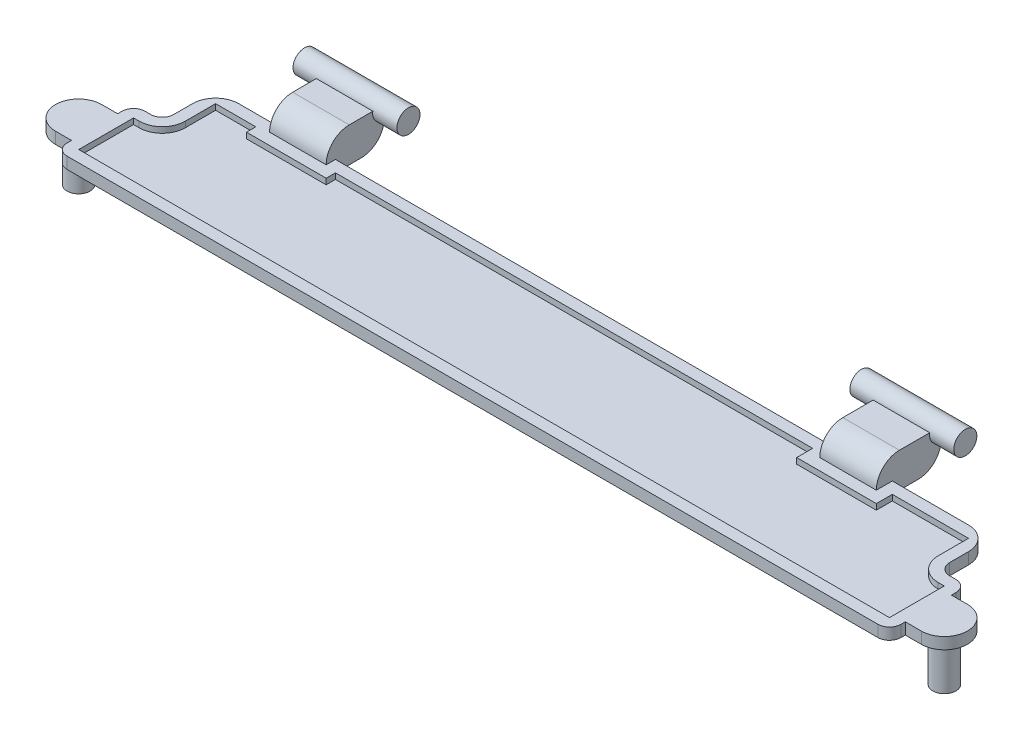
SolidWorks part; units mm, degrees
material "Alloy Steel"
ref_plane "Front Plane" through (0, 0, 0) normal (0, 0, 1) x (1, 0, 0)
ref_plane "Top Plane" through (0, 0, 0) normal (0, 1, 0) x (1, 0, 0)
ref_plane "Right Plane" through (0, 0, 0) normal (1, 0, 0) x (0, 0, -1)
sketch "Sketch1" plane through (0, 0, 0) normal (0, 1, 0) x (1, 0, 0)
  line L0 (0, 0) -> (67.22, 0) construction
  circle A0 centre (67.22, 0) radius 2
  circle A1 centre (0, 0) radius 2
extrude "Boss-Extrude1" add sketch "Sketch1" along normal blind 2.5
sketch "Sketch2" plane through (0, 2.5, 0) normal (0, 1, 0) x (1, 0, 0)
  line L3 (0, 3.3731) -> (0, 8)
  line L4 (0, 8) -> (67.2203, 8)
  line L5 (67.2203, 3.3731) -> (67.2203, 8)
  line L6 (69.7452, -3.3731) -> (-2.4854, -3.3731)
  line L7 (69.7452, -3.3731) -> (69.7452, 3.3731)
  line L8 (69.7452, 3.3731) -> (67.2203, 3.3731)
  line L9 (-2.4854, -3.3731) -> (-2.4854, 3.3731)
  line L12 (0, 3.3731) -> (-2.4854, 3.3731)
  point P4 (32.05, 0)
  point P7 (32.05, 0)
extrude "Boss-Extrude3" add sketch "Sketch2" along normal blind 1
fillet "Fillet1" radius 1 6 edges at (0, 3, -3.3731) (67.2203, 3, -3.3731) (69.7452, 3, -3.3731) (69.7452, 3, 3.3731) (-2.4854, 3, 3.3731) (-2.4854, 3, -3.3731)
sketch "Sketch3" plane through (0, 3.5, 0) normal (0, 1, 0) x (1, 0, 0)
  line L0 (33.6102, 8) -> (4.9902, 8) construction
  line L1 (67.2203, 8) -> (0, 8) construction
  line L2 (33.6102, 8) -> (62.2302, 8) construction
  line L3 (4.9902, 8) -> (4.9902, 12.2253) construction
  line L4 (4.9902, 12.2253) -> (10.8698, 12.2253) construction
  line L5 (62.2302, 8) -> (62.2302, 12.2253) construction
  line L6 (62.2302, 12.2253) -> (50.1098, 12.2253) construction
  line L7 (7.93, 12.2253) -> (7.93, 7.1953) construction
  line L8 (56.17, 12.2253) -> (56.17, 6.616) construction
  line L9 (10.8698, 12.2253) -> (50.1115, 12.2253) construction
  line L10 (5.48, 7.1953) -> (10.38, 7.1953)
  line L11 (5.48, 7.1953) -> (5.48, 12.2253)
  line L12 (5.48, 12.2253) -> (10.38, 12.2253)
  line L13 (10.38, 7.1953) -> (10.38, 12.2253)
  line L14 (5.48, 7.1953) -> (10.38, 12.2253) construction
  line L15 (5.48, 12.2253) -> (10.38, 7.1953) construction
  line L16 (58.62, 6.616) -> (53.72, 6.616)
  line L17 (58.62, 6.616) -> (58.62, 12.2253)
  line L18 (58.62, 12.2253) -> (53.72, 12.2253)
  line L19 (53.72, 6.616) -> (53.72, 12.2253)
  line L20 (58.62, 6.616) -> (53.72, 12.2253) construction
  line L21 (58.62, 12.2253) -> (53.72, 6.616) construction
  point P13 (7.93, 9.7103)
  point P18 (56.17, 9.4207)
  dimension "D1" = 28.62
extrude "Boss-Extrude4" add sketch "Sketch3" along normal blind 2 and the other way blind 1
sketch "Sketch4" plane through (5.48, 0, 0) normal (-1, 0, 0) x (0, 0, 1)
  line L0 (-12.2253, 2.5) -> (-12.2253, 5.5) construction
  circle A0 centre (-12.2253, 5.3165) radius 1
extrude "Boss-Extrude5" add sketch "Sketch4" along normal blind 2 and the other way blind 7
sketch "Sketch5" plane through (53.72, 0, 0) normal (-1, 0, 0) x (0, 0, 1)
  circle A0 centre (-12.2253, 5.3165) radius 1
extrude "Boss-Extrude6" add sketch "Sketch5" along normal blind 2 and the other way blind 7
fillet "Fillet2" radius 2 2 edges at (7.93, 5.5, -7.1953) (56.17, 5.5, -6.616)
fillet "Fillet3" radius 2 1 edges at (56.17, 2.5, -12.2253)
sketch "Sketch6" plane through (0, 3.5, 0) normal (0, 1, 0) x (1, 0, 0)
  line L32 (59.62, 5.616) -> (52.72, 5.616)
  line L33 (59.62, 5.616) -> (52.72, 5.616)
  line L34 (52.72, 7) -> (11.38, 7)
  line L35 (11.38, 7) -> (11.38, 6.1953)
  line L36 (52.72, 5.616) -> (52.72, 7)
  line L37 (4.48, 6.1953) -> (4.48, 7)
  line L38 (4.48, 7) -> (1, 7)
  line L39 (1, 7) -> (1, 4.3731)
  line L40 (-1, 2.3731) -> (-1.4854, 2.3731)
  line L41 (-1.4854, 2.3731) -> (-1.4854, -2.3731)
  line L42 (-1.4854, -2.3731) -> (68.7452, -2.3731)
  line L43 (68.7452, -2.3731) -> (68.7452, 2.3731)
  line L44 (68.7452, 2.3731) -> (68.2203, 2.3731)
  line L45 (66.2203, 4.3731) -> (66.2203, 7)
  line L46 (66.2203, 7) -> (59.62, 7)
  line L47 (52.72, 5.616) -> (52.72, 7)
  line L48 (11.38, 6.1953) -> (4.48, 6.1953)
  line L49 (59.62, 7) -> (59.62, 5.616)
  line L50 (52.72, 7) -> (11.38, 7)
  line L51 (11.38, 7) -> (11.38, 6.1953)
  line L52 (11.38, 6.1953) -> (4.48, 6.1953)
  line L53 (4.48, 6.1953) -> (4.48, 7)
  line L54 (4.48, 7) -> (1, 7)
  line L55 (1, 7) -> (1, 4.3731)
  line L56 (-1, 2.3731) -> (-1.4854, 2.3731)
  line L57 (-1.4854, 2.3731) -> (-1.4854, -2.3731)
  line L58 (-1.4854, -2.3731) -> (68.7452, -2.3731)
  line L59 (68.7452, -2.3731) -> (68.7452, 2.3731)
  line L60 (68.7452, 2.3731) -> (68.2203, 2.3731)
  line L61 (66.2203, 4.3731) -> (66.2203, 7)
  line L62 (66.2203, 7) -> (59.62, 7)
  line L63 (59.62, 7) -> (59.62, 5.616)
  arc A12 (-1, 2.3731) -> (1, 4.3731) centre (-1, 4.3731) ccw
  arc A13 (66.2203, 4.3731) -> (68.2203, 2.3731) centre (68.2203, 4.3731) ccw
  arc A14 (-1, 2.3731) -> (1, 4.3731) centre (-1, 4.3731) ccw
  arc A15 (66.2203, 4.3731) -> (68.2203, 2.3731) centre (68.2203, 4.3731) ccw
  dimension "D1" = 1
extrude "Cut-Extrude1" cut sketch "Sketch6" against normal blind 0.5
fillet "Fillet4" radius 2 1 edges at (7.93, 2.5, -12.2253)
fillet "Fillet6" radius 2 2 edges at (0, 3, -8) (67.2203, 3, -8)
sketch "Sketch7" plane through (0, 2.5, 0) normal (0, -1, 0) x (1, 0, 0)
  line L1 (70.7055, 9.1582) -> (-6.3422, 9.1582)
  line L2 (70.7055, 9.1582) -> (70.7055, -4.3106)
  line L3 (70.7055, -4.3106) -> (-6.3422, -4.3106)
  line L4 (-6.3422, 9.1582) -> (-6.3422, -4.3106)
  line L5 (70.7055, 9.1582) -> (-6.3422, -4.3106) construction
  line L6 (70.7055, -4.3106) -> (-6.3422, 9.1582) construction
  point P0 (32.1816, 2.4238)
extrude "Cut-Extrude2" cut sketch "Sketch7" along normal blind 10
sketch "Sketch8" plane through (0, 2.5, 0) normal (0, -1, 0) x (-1, 0, 0)
  line L0 (-33.6299, -3.3731) -> (-33.6299, 8) construction
  line L1 (1.4854, -3.3731) -> (-68.7452, -3.3731) construction
  line L2 (-53.72, 8) -> (-10.38, 8) construction
  line L3 (-33.6299, 0) -> (3.8701, 0) construction
  line L4 (-33.6299, 0) -> (-71.1299, 0) construction
  circle A0 centre (3.8701, 0) radius 1
  circle A1 centre (-71.1299, 0) radius 1
extrude "Boss-Extrude7" add sketch "Sketch8" along normal blind 4 separate body
sketch "Sketch9" plane through (0, 2.5, 0) normal (0, -1, 0) x (1, 0, 0)
  line L0 (-3.8701, 2) -> (71.1299, 2)
  line L1 (-3.8701, -2) -> (71.1299, -2)
  arc A0 (-3.8701, 2) -> (-3.8701, -2) centre (-3.8701, 0) ccw
  arc A1 (71.1299, -2) -> (71.1299, 2) centre (71.1299, 0) ccw
extrude "Boss-Extrude8" add sketch "Sketch9" against normal blind 1
sketch "Sketch10" plane through (0, 3, 0) normal (0, 1, 0) x (1, 0, 0)
  line L0 (68.7452, -2.3731) -> (68.7452, -2) construction
  line L1 (-1.4854, 2) -> (68.7452, 2)
  line L2 (-1.4854, 2) -> (-1.4854, -2.1865)
  line L3 (-1.4854, -2.1865) -> (68.7452, -2.1865)
  line L4 (68.7452, 2) -> (68.7452, -2.1865)
extrude "Cut-Extrude4" cut sketch "Sketch10" along normal blind 1
equation "\"2.1.00mm\"=3"
equation "\"z\"=2"
equation "\"zz\"=2"
